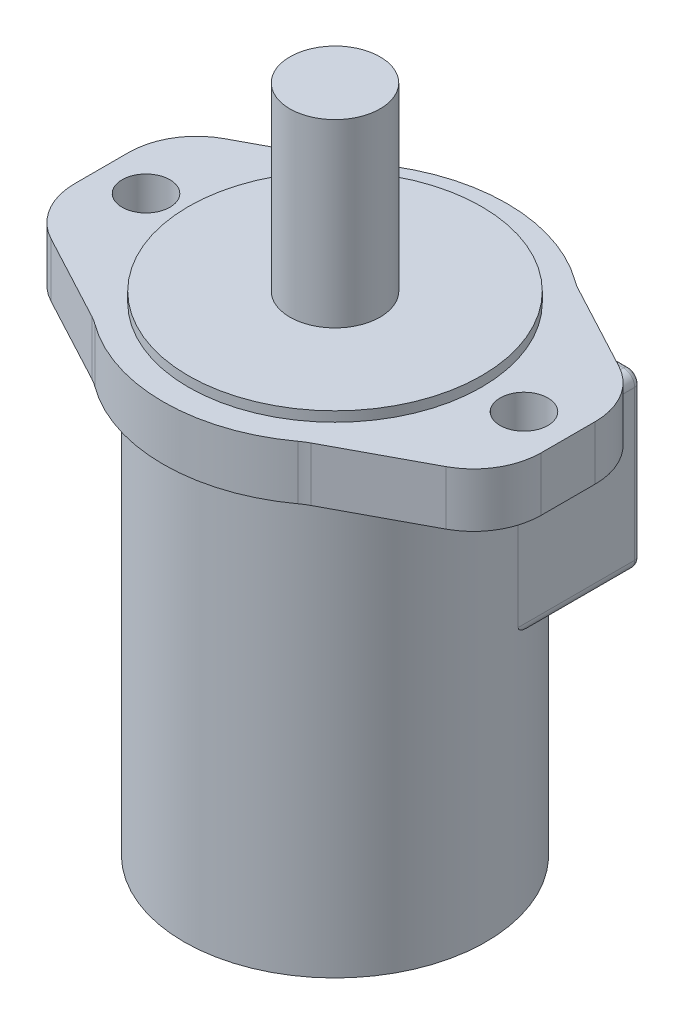
SolidWorks part; units mm, degrees
ref_plane "Front Plane" through (0, 0, 0) normal (0, 0, 1) x (1, 0, 0)
ref_plane "Top Plane" through (0, 0, 0) normal (0, 1, 0) x (1, 0, 0)
ref_plane "Right Plane" through (0, 0, 0) normal (1, 0, 0) x (0, 0, -1)
ref_axis "Axis1" through (0, -146.4913, 0) along (0, 1, 0)
sketch "Sketch1" plane through (0, 0, 0) normal (0, 1, 0) x (1, 0, 0)
  circle A0 centre (0, 0) radius 41.275
  dimension "D1" = 82.55
extrude "Boss-Extrude1" add sketch "Sketch1" along normal blind 2.794
sketch "Sketch2" plane through (0, 0, 0) normal (0, 1, 0) x (1, 0, 0)
  circle A0 centre (0, 0) radius 42.545
  dimension "D1" = 85.09
extrude "Boss-Extrude2" add sketch "Sketch2" against normal blind 134.62
sketch "Sketch3" plane through (0, -134.62, 0) normal (0, -1, 0) x (1, 0, 0)
  line L1 (2.7496, -36.6756) -> (5.4993, -31.9131)
  line L2 (5.4993, -31.9131) -> (2.7496, -27.1506)
  line L3 (2.7496, -27.1506) -> (-2.7496, -27.1506)
  line L4 (-2.7496, -27.1506) -> (-5.4993, -31.9131)
  line L5 (-5.4993, -31.9131) -> (-2.7496, -36.6756)
  line L6 (-2.7496, -36.6756) -> (2.7496, -36.6756)
  circle A0 centre (0, -31.9131) radius 4.7625 construction
extrude "Boss-Extrude3" add sketch "Sketch3" along normal blind 4.7625
chamfer "Chamfer1" distance 0.7937 angle 45 6 edges at (-4.1244, -139.3825, -34.2943) (-4.1244, -139.3825, -29.5318) (0, -139.3825, -27.1506) (4.1244, -139.3825, -29.5318) (4.1244, -139.3825, -34.2943) (0, -139.3825, -36.6756)
pattern_circular "CirPattern1" count 7 over 360 about axis through (0, -146.4913, 0) along (0, 1, 0) of "Boss-Extrude3", "Chamfer1"
sketch "Sketch4" plane through (0, -134.62, 0) normal (0, -1, 0) x (1, 0, 0)
  circle A0 centre (0, 0) radius 3.175
  dimension "D1" = 6.35
extrude "Cut-Extrude1" cut sketch "Sketch4" against normal blind 9.525
sketch "Sketch5" plane through (0, 0, 0) normal (0, 1, 0) x (1, 0, 0)
  line L0 (-65.659, 0) -> (65.659, 0) construction
  line L1 (-65.659, 19.0067) -> (-65.659, -19.0067)
  line L2 (65.659, 19.0067) -> (65.659, -19.0067)
  line L3 (-65.659, 19.0067) -> (-29.5915, 38.2838)
  line L4 (-65.659, -19.0067) -> (-29.5915, -38.2838)
  line L5 (0, 0) -> (0, 36.8538) construction
  line L6 (65.659, -19.0067) -> (29.5915, -38.2838)
  line L7 (65.659, 19.0067) -> (29.5915, 38.2838)
  arc A0 (29.5915, 38.2838) -> (-29.5915, 38.2838) centre (0, 0) ccw
  circle A1 centre (-53.213, 0) radius 6.731
  circle A2 centre (53.213, 0) radius 6.731
  arc A3 (-29.5915, -38.2838) -> (29.5915, -38.2838) centre (0, 0) ccw
  dimension "D1" = 48.387
  dimension "D3" = 13.462
  dimension "D4" = 53.213
  dimension "D5" = 53.213
  dimension "D2" = 131.318
extrude "Boss-Extrude4" add sketch "Sketch5" against normal blind 15.24
fillet "Fillet1" radius 19.05 8 edges at (-29.5915, -7.62, 38.2838) (29.5915, -7.62, 38.2838) (65.659, -7.62, 19.0067) (65.659, -7.62, -19.0067) (29.5915, -7.62, -38.2838) (-29.5915, -7.62, -38.2838) (-65.659, -7.62, 19.0067) (-65.659, -7.62, -19.0067)
sketch "Sketch6" plane through (0, 0, 0) normal (0, 0, 1) x (1, 0, 0)
  line L1 (41.275, -66.929) -> (-41.275, -66.929)
  line L2 (41.275, -66.929) -> (41.275, -18.415)
  line L3 (41.275, -18.415) -> (-41.275, -18.415)
  line L4 (-41.275, -66.929) -> (-41.275, -18.415)
  line L6 (0, -18.415) -> (0, -66.929) construction
  line L7 (0, -146.4913) -> (0, 9.9028) construction
  line L8 (41.275, -42.672) -> (-41.275, -42.672) construction
  line L9 (55.5886, 0) -> (30.8819, 0) construction
  line L10 (-42.545, -15.24) -> (42.545, -15.24) construction
  circle A0 centre (22.86, -42.672) radius 6.35
  circle A1 centre (-22.86, -42.672) radius 6.35
  dimension "D2" = 12.7
  dimension "D3" = 22.86
  dimension "D4" = 42.672
  dimension "D1" = 82.55
  dimension "D5" = 3.175
extrude "Boss-Extrude5" add sketch "Sketch6" against normal blind 44.704
fillet "Fillet2" radius 3.175 4 edges at (41.275, -18.415, -27.5108) (-41.275, -18.415, -27.5108) (-41.275, -66.929, -27.5108) (41.275, -66.929, -27.5108)
fillet "Fillet3" radius 1.5875 8 edges at (40.3451, -65.9991, -44.704) (0, -66.929, -44.704) (-40.3451, -65.9991, -44.704) (-41.275, -42.672, -44.704) (-40.3451, -19.3449, -44.704) (0, -18.415, -44.704) (40.3451, -19.3449, -44.704) (41.275, -42.672, -44.704)
sketch "Sketch7" plane through (0, 2.794, 0) normal (0, 1, 0) x (-1, 0, 0)
  circle A0 centre (0, 0) radius 12.7
  dimension "D1" = 25.4
extrude "Boss-Extrude6" add sketch "Sketch7" along normal blind 50.8
hole_wizard "1/2 NPT Tapped Hole1" positions "Sketch9" profile "Sketch8" size "1/2" standard "Ansi Inch"
sketch "Sketch9" plane through (0, 0, -44.704) normal (0, 0, -1) x (-1, 0, 0)
  circle A0 centre (-22.86, -42.672) radius 6.35 construction
  point P0 (-22.86, -42.672)
sketch "Sketch8" plane through (22.86, -42.672, -44.704) normal (1, 0, 0) x (0, 1, 0)
  line L0 (0, 0) -> (0, 28.4785)
  line L1 (8.9281, 23.114) -> (0, 28.4785)
  line L2 (-8.9281, 23.114) -> (0, 28.4785) construction
  line L3 (8.9281, 23.114) -> (8.9281, 13.462)
  line L4 (8.9281, 13.462) -> (9.4797, 13.462)
  line L5 (9.4797, 13.462) -> (9.8828, 0)
  line L6 (-9.4797, 13.462) -> (-9.8828, 0) construction
  line L7 (9.8828, 0) -> (0, 0)
  line L8 (0, -6.35) -> (0, 107.95) construction
  line L11 (-8.9281, 13.462) -> (-9.4797, 13.462) construction
  dimension "Tap Drill Dia." = 17.8562
  dimension "Tap Drill Depth" = 23.114
  dimension "Thread Dia." = 19.7656
  dimension "Thread Angle" = 3.43
  dimension "Thread Depth" = 13.462
  dimension "Drill Angle" = 118
cosmetic thread "Hole Thread1" parameters "D1"=13.462
hole_wizard "1/2 NPT Tapped Hole2" positions "Sketch11" profile "Sketch10" size "1/2" standard "Ansi Inch"
sketch "Sketch11" plane through (0, 0, -44.704) normal (0, 0, -1) x (-1, 0, 0)
  circle A0 centre (22.86, -42.672) radius 6.35 construction
  point P0 (22.86, -42.672)
sketch "Sketch10" plane through (-22.86, -42.672, -44.704) normal (1, 0, 0) x (0, 1, 0)
  line L0 (0, 0) -> (0, 28.4785)
  line L1 (8.9281, 23.114) -> (0, 28.4785)
  line L2 (-8.9281, 23.114) -> (0, 28.4785) construction
  line L3 (8.9281, 23.114) -> (8.9281, 13.462)
  line L4 (8.9281, 13.462) -> (9.4797, 13.462)
  line L5 (9.4797, 13.462) -> (9.8828, 0)
  line L6 (-9.4797, 13.462) -> (-9.8828, 0) construction
  line L7 (9.8828, 0) -> (0, 0)
  line L8 (0, -6.35) -> (0, 107.95) construction
  line L11 (-8.9281, 13.462) -> (-9.4797, 13.462) construction
  dimension "Tap Drill Dia." = 17.8562
  dimension "Tap Drill Depth" = 23.114
  dimension "Thread Dia." = 19.7656
  dimension "Thread Angle" = 3.43
  dimension "Thread Depth" = 13.462
  dimension "Drill Angle" = 118
cosmetic thread "Hole Thread2" parameters "D1"=13.462
hole_wizard "7/16-20 Tapped Hole1" positions "Sketch13" profile "Sketch12" tap size "7/16-20" standard "Ansi Inch"
sketch "Sketch13" plane through (0, -134.62, 0) normal (0, -1, 0) x (1, 0, 0)
  circle A0 centre (0, 0) radius 3.175 construction
  point P0 (0, 0)
sketch "Sketch12" plane through (0, -134.62, 0) normal (1, 0, 0) x (0, 0, -1)
  line L0 (0, 0) -> (0, 31.6826)
  line L1 (0, 31.6826) -> (4.9606, 28.702)
  line L2 (4.9606, 28.702) -> (4.9606, 0)
  line L5 (4.9606, 0) -> (0, 0)
  line L10 (0, 31.6826) -> (-4.9606, 28.702) construction
  line L11 (0, -6.35) -> (0, 107.95) construction
  dimension "Tap Drill Dia." = 9.9212
  dimension "Tap Drill Depth" = 28.702
  dimension "Drill Angle" = 118
cosmetic thread "Hole Thread3" parameters "D1"=22.352, "D2"=11.1125
